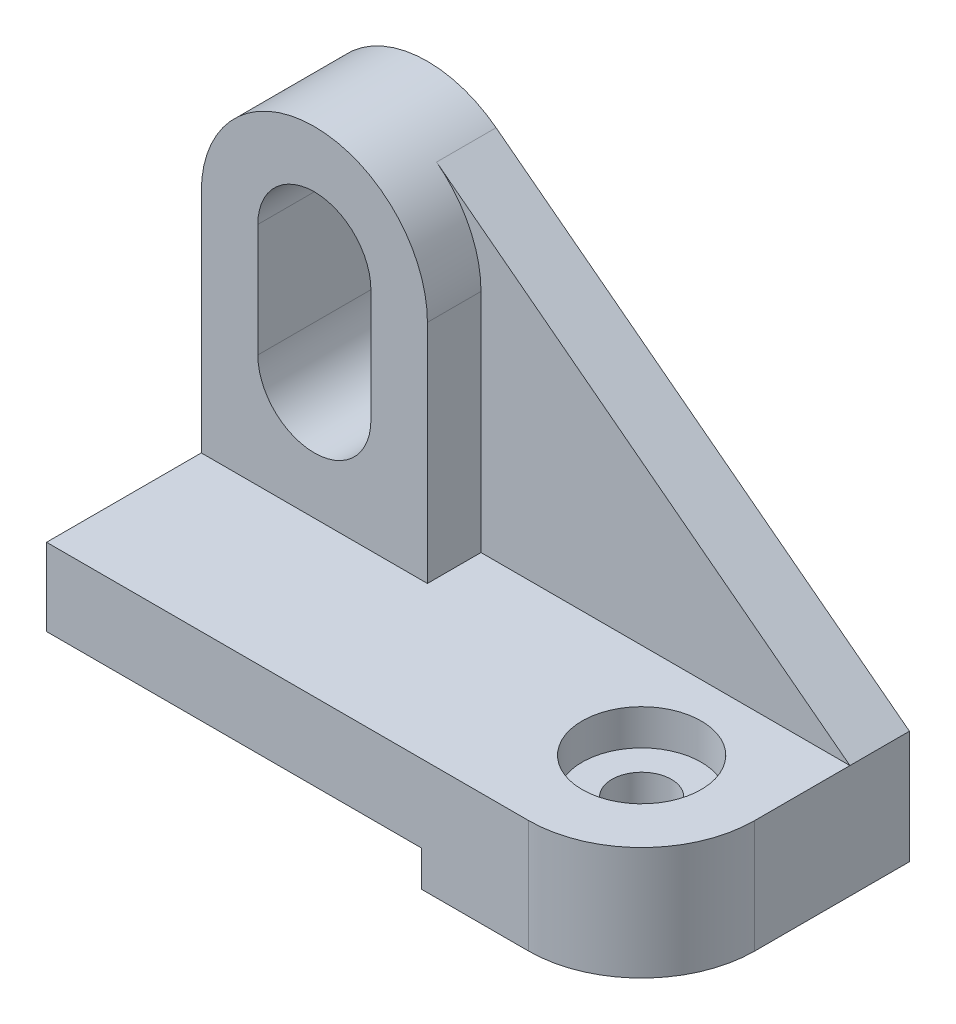
SolidWorks part; units mm, degrees
ref_plane "Front Plane" through (0, 0, 0) normal (0, 0, 1) x (1, 0, 0)
ref_plane "Top Plane" through (0, 0, 0) normal (0, 1, 0) x (1, 0, 0)
ref_plane "Right Plane" through (0, 0, 0) normal (1, 0, 0) x (0, 0, -1)
sketch "Sketch1" plane through (0, 0, 0) normal (0, 0, 1) x (1, 0, 0)
  line L4 (0, 0) -> (63, 0)
  line L5 (63, 0) -> (63, -6)
  line L10 (63, -6) -> (100, -6)
  line L11 (100, -6) -> (100, 13)
  line L12 (100, 13) -> (0, 13)
  line L13 (0, 13) -> (0, 0)
  line L14 (30.5385, 66.0952) -> (100, 13)
  line L15 (0, 13) -> (38, 13)
  line L16 (0, 13) -> (0, 51)
  line L18 (38, 13) -> (38, 51)
  line L20 (9.5, 51) -> (9.5, 32)
  line L22 (28.5, 51) -> (28.5, 32)
  arc A0 (38, 51) -> (0, 51) centre (19, 51) ccw
  arc A1 (28.5, 51) -> (9.5, 51) centre (19, 51) ccw
  arc A2 (9.5, 32) -> (28.5, 32) centre (19, 32) ccw
  point P11 (19, 41.5)
  dimension "D5" = 38
  dimension "D8" = 19
  dimension "D1" = 63
  dimension "D2" = 37
  dimension "D3" = 6
  dimension "D4" = 13
  dimension "D6" = 38
  dimension "D7" = 19
extrude "Boss-Extrude1" add sketch "Sketch1" along normal blind 45 contours L12 L13 L4 L5 L10 L11 region at (54.5946, 5.1143, 0)
extrude "Boss-Extrude2" add sketch "Sketch1<3>" along normal blind 19 contours L18 A0 L16 L12 A2 L20 A1 L22 region at (0.6851, 32, 0)
sketch "Sketch1<3>" plane through (0, 0, 0) normal (0, 0, 1) x (1, 0, 0) same geometry as "Sketch1"
extrude "Boss-Extrude3" add sketch "Sketch1<4>" along normal blind 10 contours A0 L18 L12 L14 region at (58.476, 29.0618, 0)
sketch "Sketch1<4>" plane through (0, 0, 0) normal (0, 0, 1) x (1, 0, 0) same geometry as "Sketch1"
fillet "Fillet1" radius 19 1 edges at (100, 3.5, 45)
hole_wizard "CBORE for M5 Hex Head Bolt1" positions "Sketch5" profile "Sketch4" counterbore size "M5" standard "ISO"
sketch "Sketch5" plane through (0, 13, 0) normal (0, 1, 0) x (1, 0, 0)
  point P0 (81, -26)
sketch "Sketch4" plane through (81, 13, 26) normal (1, 0, 0) x (0, 0, 1)
  line L0 (0, 0) -> (0, 22.8868)
  line L1 (0, 22.8868) -> (5, 20)
  line L2 (5, 20) -> (5, 6)
  line L3 (5, 6) -> (10, 6)
  line L4 (10, 6) -> (10, 0)
  line L5 (10, 0) -> (0, 0)
  line L10 (0, 22.8868) -> (-5, 20) construction
  line L11 (0, -6.35) -> (0, 107.95) construction
  dimension "Hole Dia." = 10
  dimension "Hole Depth" = 20
  dimension "C'Bore Dia." = 20
  dimension "C'Bore Depth" = 6
  dimension "Drill Angle" = 120
